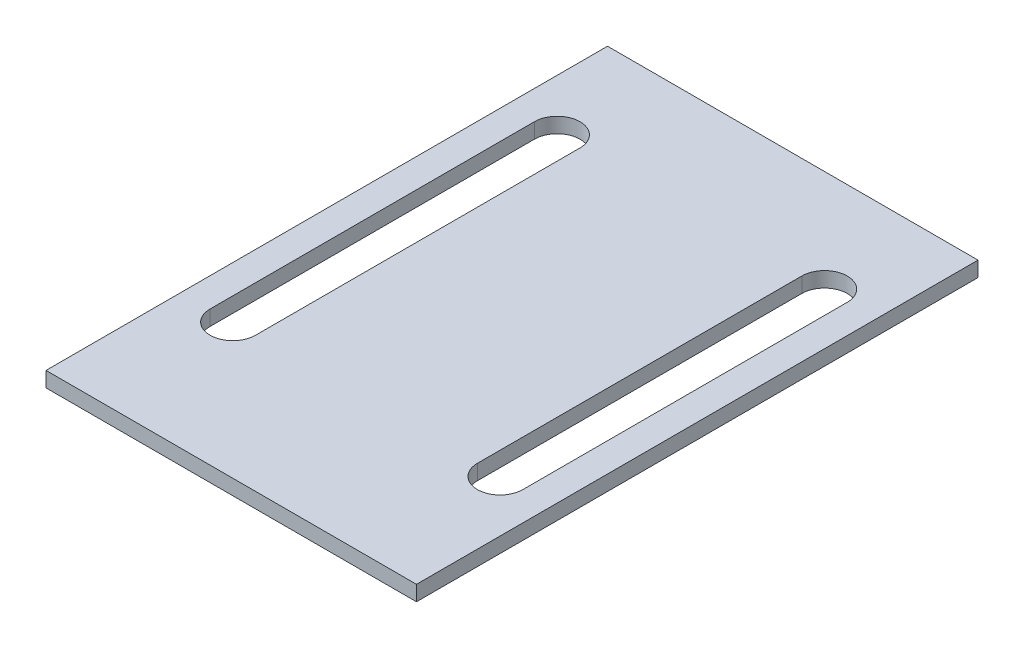
SolidWorks part; units mm, degrees
ref_plane "Front" through (0, 0, 0) normal (0, 0, 1) x (1, 0, 0)
ref_plane "Top" through (0, 0, 0) normal (0, 1, 0) x (1, 0, 0)
ref_plane "Right" through (0, 0, 0) normal (1, 0, 0) x (0, 0, -1)
sketch "Sketch1" plane through (0, 0, 0) normal (0, 1, 0) x (1, 0, 0)
  line L1 (0, 0) -> (122.1, 0)
  line L2 (0, 0) -> (0, 197.8)
  line L3 (0, 197.8) -> (122.1, 197.8)
  line L4 (122.1, 0) -> (122.1, 197.8)
  dimension "D1" = 122.1
  dimension "D2" = 197.8
extrude "Boss-Extrude2" add sketch "Sketch1" along normal blind 5 contours L2 L3 L4 L1
sketch "Sketch3" plane through (0, 5, 0) normal (0, 1, 0) x (1, 0, 0)
  line L3 (17, 152.2216) -> (17, 45.3016) construction
  line L4 (24.5, 152.2216) -> (24.5, 45.3016)
  line L5 (9.5, 152.2216) -> (9.5, 45.3016)
  line L8 (61.05, 197.8) -> (61.05, 0)
  line L9 (0, 197.8) -> (122.1, 197.8) construction
  line L10 (0, 0) -> (122.1, 0) construction
  line L11 (105.1, 152.2216) -> (105.1, 45.3016) construction
  line L12 (97.6, 152.2216) -> (97.6, 45.3016)
  line L13 (112.6, 152.2216) -> (112.6, 45.3016)
  arc A2 (24.5, 152.2216) -> (9.5, 152.2216) centre (17, 152.2216) ccw
  arc A3 (9.5, 45.3016) -> (24.5, 45.3016) centre (17, 45.3016) ccw
  arc A4 (97.6, 152.2216) -> (112.6, 152.2216) centre (105.1, 152.2216) cw
  arc A5 (112.6, 45.3016) -> (97.6, 45.3016) centre (105.1, 45.3016) cw
  point P0 (17, 37.8016)
  point P1 (17, 159.7216)
  point P9 (17, 98.7616)
  point P27 (105.1, 98.7616)
  dimension "D1" = 121.92
  dimension "D3" = 15
extrude "Cut-Extrude1" cut sketch "Sketch3" against normal blind 5 contours A5 L13 A4 L12 | L5 A3 L4 A2 region at (17, 5, -98.7616) region at (105.1, 5, -98.7616)
sketch "Sketch5" plane through (0, 0, -197.8) normal (0, 0, -1) x (-1, 0, 0)
  line L1 (41.638, -41.5201) -> (-135.0546, -41.5201)
  line L2 (41.638, -41.5201) -> (41.638, 26.3146)
  line L3 (41.638, 26.3146) -> (-135.0546, 26.3146)
  line L4 (-135.0546, -41.5201) -> (-135.0546, 26.3146)
extrude "Cut-Extrude2" cut sketch "Sketch5" against normal blind 12
sketch "Sketch6" plane through (0, 0, 0) normal (0, 0, 1) x (1, 0, 0)
  line L1 (-6.1951, 32.8599) -> (142.3082, 32.8599)
  line L2 (-6.1951, 32.8599) -> (-6.1951, -30.9989)
  line L3 (-6.1951, -30.9989) -> (142.3082, -30.9989)
  line L4 (142.3082, 32.8599) -> (142.3082, -30.9989)
extrude "Cut-Extrude3" cut sketch "Sketch6" against normal blind 19
sketch "Sketch10" plane through (0, 0, -19) normal (0, 0, 1) x (1, 0, 0)
  line L1 (0, 5) -> (122.1, 5)
  line L2 (0, 5) -> (0, 0)
  line L3 (0, 0) -> (122.1, 0)
  line L4 (122.1, 5) -> (122.1, 0)
extrude "Boss-Extrude4" add sketch "Sketch10" along normal blind 18.27
